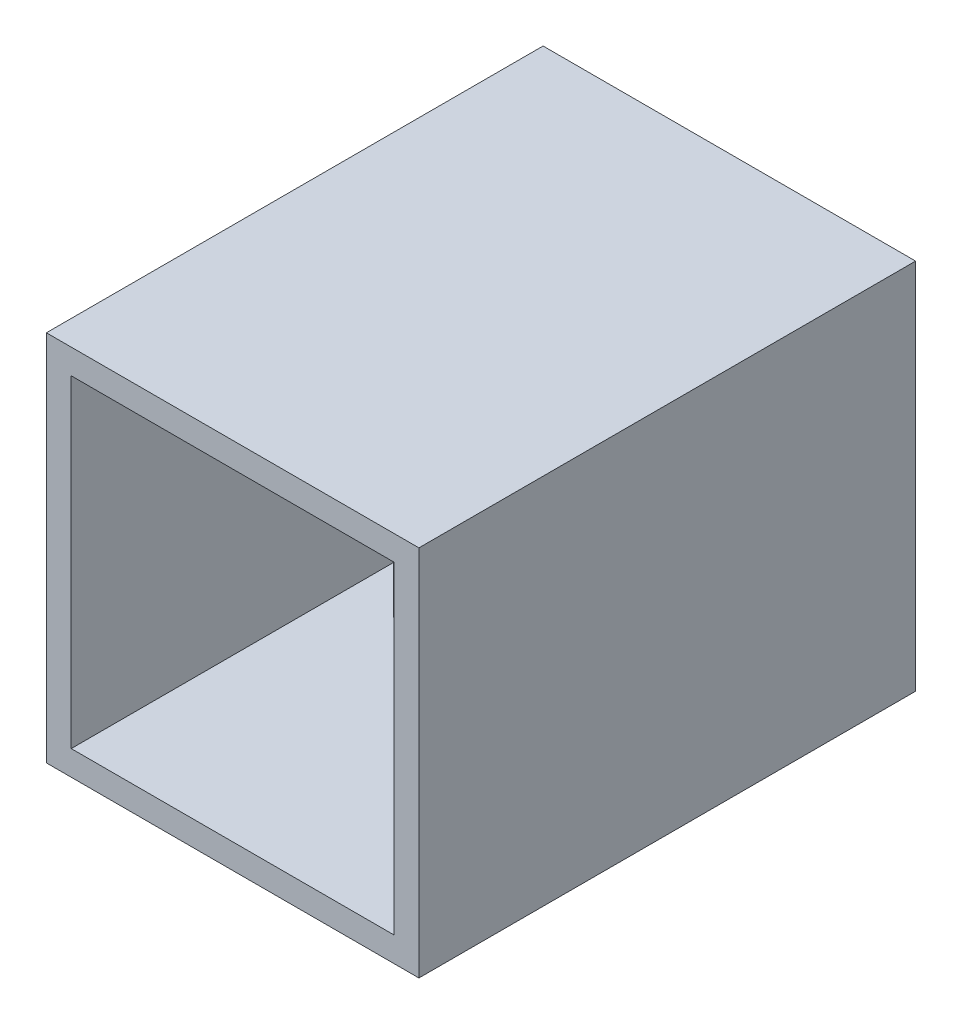
SolidWorks part; units mm, degrees
ref_plane "Front Plane" through (0, 0, 0) normal (0, 0, 1) x (1, 0, 0)
ref_plane "Top Plane" through (0, 0, 0) normal (0, 1, 0) x (1, 0, 0)
ref_plane "Right Plane" through (0, 0, 0) normal (1, 0, 0) x (0, 0, -1)
sketch "Sketch1" plane through (0, 0, 0) normal (0, 0, 1) x (1, 0, 0)
  line L1 (0, 0) -> (1500, 0)
  line L2 (0, 0) -> (0, 1500)
  line L3 (0, 1500) -> (1500, 1500)
  line L4 (1500, 0) -> (1500, 1500)
  line L5 (100, 1400) -> (1400, 1400)
  line L6 (100, 1400) -> (100, 100)
  line L7 (100, 100) -> (1400, 100)
  line L8 (1400, 1400) -> (1400, 100)
  dimension "D1" = 1500
  dimension "D2" = 1500
  dimension "D3" = 100
  dimension "D4" = 100
  dimension "D5" = 100
  dimension "D6" = 100
extrude "Boss-Extrude1" add sketch "Sketch1" along normal blind 2000 contours L1 L4 L3 L2 L5 L8 L7 L6 region at (21.2132, 750, 0)
sketch "Sketch2" plane through (0, 1400, 0) normal (0, -1, 0) x (1, 0, 0)
  circle A0 centre (750, 1000) radius 250
  dimension "D1" = 500
extrude "Boss-Extrude2" add sketch "Sketch2" along normal blind 1000
